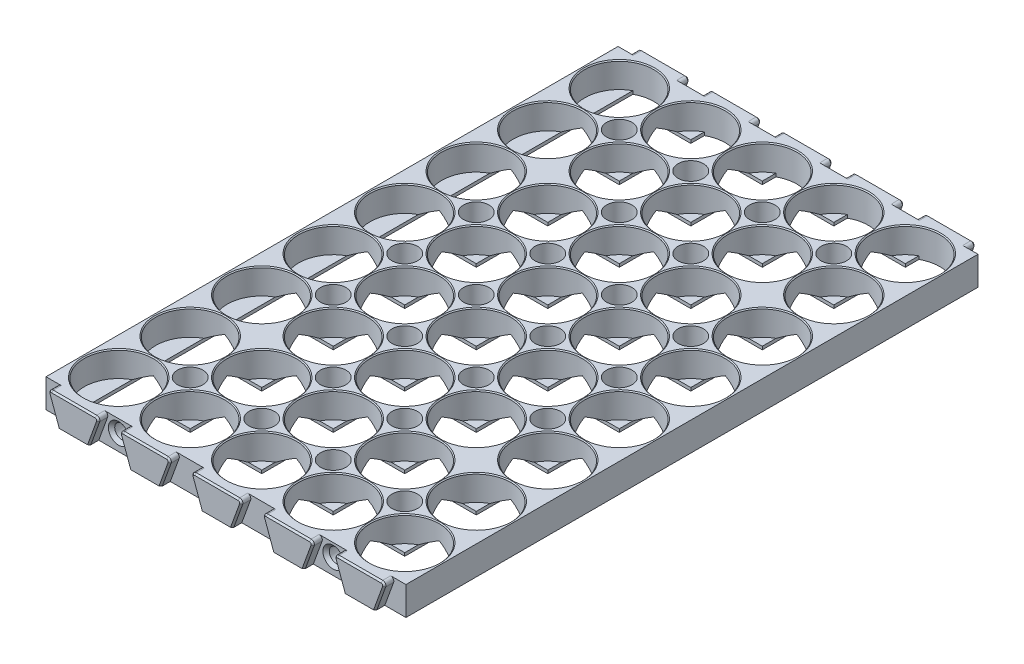
SolidWorks part; units mm, degrees
ref_plane "Front Plane" through (0, 0, 0) normal (0, 0, 1) x (1, 0, 0)
ref_plane "Top Plane" through (0, 0, 0) normal (0, 1, 0) x (1, 0, 0)
ref_plane "Right Plane" through (0, 0, 0) normal (1, 0, 0) x (0, 0, -1)
sketch "Sketch1" plane through (0, 0, 0) normal (0, 1, 0) x (1, 0, 0)
  line L0 (-11.25, 10.875) -> (11.25, 10.875) construction
  line L1 (-11.25, -11.25) -> (11.25, -11.25)
  line L2 (-11.25, -11.25) -> (-11.25, 11.25)
  line L3 (-11.25, 11.25) -> (11.25, 11.25)
  line L4 (11.25, -11.25) -> (11.25, 11.25)
  line L5 (-11.25, -11.25) -> (11.25, 11.25) construction
  line L6 (-11.25, 11.25) -> (11.25, -11.25) construction
  circle A0 centre (0, 0) radius 10.875
  point P0 (0, 0)
  dimension "D1" = 21.75
  dimension "D2" = 22.5
  dimension "D3" = 0.375
extrude "Boss-Extrude1" add sketch "Sketch1" along normal blind 8
sketch "Sketch2" plane through (0, 0, 0) normal (0, -1, 0) x (1, 0, 0)
  line L0 (5.25, 11.25) -> (-5.25, 11.25) construction
  line L1 (11.25, 11.25) -> (5.25, 11.25)
  line L2 (11.25, 11.25) -> (11.25, 5.25)
  line L3 (11.25, 5.25) -> (5.25, 5.25)
  line L4 (5.25, 11.25) -> (5.25, 5.25)
  line L5 (11.25, -11.25) -> (5.25, -11.25)
  line L6 (11.25, -11.25) -> (11.25, -5.25)
  line L7 (11.25, -5.25) -> (5.25, -5.25)
  line L8 (5.25, -11.25) -> (5.25, -5.25)
  line L9 (-11.25, -11.25) -> (-5.25, -11.25)
  line L10 (-11.25, -11.25) -> (-11.25, -5.25)
  line L11 (-11.25, -5.25) -> (-5.25, -5.25)
  line L12 (-5.25, -11.25) -> (-5.25, -5.25)
  line L13 (-11.25, 11.25) -> (-5.25, 11.25)
  line L14 (-11.25, 11.25) -> (-11.25, 5.25)
  line L15 (-11.25, 5.25) -> (-5.25, 5.25)
  line L16 (-5.25, 11.25) -> (-5.25, 5.25)
  line L17 (11.25, 5.25) -> (11.25, -5.25) construction
  line L18 (5.25, -11.25) -> (-5.25, -11.25) construction
  line L19 (-11.25, 5.25) -> (-11.25, -5.25) construction
  dimension "D1" = 10.5
extrude "Boss-Extrude2" add sketch "Sketch2" along normal blind 1
chamfer "Chamfer2" distance 0.3 angle 45 1 edges at (0, 8, 10.875)
pattern_linear "LPattern1" count 8 spacing 22.5 along (0, 0, 1) count 5 spacing 22.5 along (1, 0, 0) of "Boss-Extrude2", "Boss-Extrude1", "Chamfer2"
sketch "Sketch5" plane through (0, 0, -5.25) normal (0, 0, 1) x (1, 0, 0)
  line L25 (-5.25, -1) -> (-5.25, 0) construction
  line L26 (-5.25, -1) -> (-11.25, -1) construction
  line L27 (-11.25, -1) -> (-11.25, 0) construction
  line L29 (-5.25, 0) -> (-9.5238, 0) construction
  line L35 (-5.25, -1) -> (-5.25, 0)
  line L36 (-5.25, -1) -> (-11.25, -1)
  line L37 (-11.25, -1) -> (-11.25, 0)
  line L39 (-5.25, 0) -> (-11.25, 0)
  line L55 (101.25, -1) -> (95.25, -1)
  line L56 (101.25, -1) -> (101.25, 0)
  line L57 (101.25, 0) -> (95.25, 0)
  line L58 (95.25, -1) -> (95.25, 0)
  dimension "D1" = 6
extrude "Boss-Extrude3" add sketch "Sketch5" along normal up to surface (174 mm away)
sketch "Sketch6" plane through (0, 0, 0) normal (0, -1, 0) x (1, 0, 0)
  line L27 (39.75, -11.25) -> (50.25, -11.25) construction
  line L28 (50.25, -11.25) -> (50.25, -9.5238) construction
  line L29 (39.75, -9.5238) -> (39.75, -11.25) construction
  line L30 (17.25, -9.5238) -> (17.25, -11.25) construction
  line L31 (17.25, -11.25) -> (27.75, -11.25) construction
  line L32 (27.75, -11.25) -> (27.75, -9.5238) construction
  line L33 (-5.25, -9.5238) -> (-5.25, -11.25) construction
  line L34 (-5.25, -11.25) -> (5.25, -11.25) construction
  line L35 (5.25, -11.25) -> (5.25, -9.5238) construction
  line L51 (39.75, -11.25) -> (50.25, -11.25)
  line L52 (50.25, -11.25) -> (50.25, -9.5238)
  line L53 (39.75, -9.5238) -> (39.75, -11.25)
  line L54 (17.25, -9.5238) -> (17.25, -11.25)
  line L55 (17.25, -11.25) -> (27.75, -11.25)
  line L56 (27.75, -11.25) -> (27.75, -9.5238)
  line L57 (-5.25, -9.5238) -> (-5.25, -11.25)
  line L58 (-5.25, -11.25) -> (5.25, -11.25)
  line L59 (5.25, -11.25) -> (5.25, -9.5238)
  line L84 (5.25, 168.75) -> (-5.25, 168.75) construction
  line L85 (-5.25, 168.75) -> (-5.25, 167.0238) construction
  line L86 (5.25, 167.0238) -> (5.25, 168.75) construction
  line L87 (27.75, 167.0238) -> (27.75, 168.75) construction
  line L88 (27.75, 168.75) -> (17.25, 168.75) construction
  line L89 (17.25, 168.75) -> (17.25, 167.0238) construction
  line L93 (50.25, 167.0238) -> (50.25, 168.75) construction
  line L94 (50.25, 168.75) -> (39.75, 168.75) construction
  line L95 (39.75, 168.75) -> (39.75, 167.0238) construction
  line L96 (5.25, 168.75) -> (-5.25, 168.75)
  line L97 (-5.25, 168.75) -> (-5.25, 167.0238)
  line L98 (5.25, 167.0238) -> (5.25, 168.75)
  line L99 (27.75, 167.0238) -> (27.75, 168.75)
  line L100 (27.75, 168.75) -> (17.25, 168.75)
  line L101 (17.25, 168.75) -> (17.25, 167.0238)
  line L105 (50.25, 167.0238) -> (50.25, 168.75)
  line L106 (50.25, 168.75) -> (39.75, 168.75)
  line L107 (39.75, 168.75) -> (39.75, 167.0238)
  line L108 (84.75, -11.25) -> (95.25, -11.25) construction
  line L109 (95.25, -11.25) -> (95.25, -9.5238) construction
  line L110 (84.75, -9.5238) -> (84.75, -11.25) construction
  line L111 (95.25, 167.0238) -> (95.25, 168.75) construction
  line L112 (95.25, 168.75) -> (84.75, 168.75) construction
  line L113 (84.75, 168.75) -> (84.75, 167.0238) construction
  line L114 (72.75, 167.0238) -> (72.75, 168.75) construction
  line L115 (72.75, 168.75) -> (62.25, 168.75) construction
  line L116 (62.25, 168.75) -> (62.25, 167.0238) construction
  line L117 (84.75, -11.25) -> (95.25, -11.25)
  line L118 (95.25, -11.25) -> (95.25, -9.5238)
  line L119 (84.75, -9.5238) -> (84.75, -11.25)
  line L120 (95.25, 167.0238) -> (95.25, 168.75)
  line L121 (95.25, 168.75) -> (84.75, 168.75)
  line L122 (84.75, 168.75) -> (84.75, 167.0238)
  line L123 (72.75, 167.0238) -> (72.75, 168.75)
  line L124 (72.75, 168.75) -> (62.25, 168.75)
  line L125 (62.25, 168.75) -> (62.25, 167.0238)
  line L129 (62.25, -11.25) -> (72.75, -11.25)
  line L130 (72.75, -11.25) -> (72.75, -9.5238)
  line L131 (62.25, -9.5238) -> (62.25, -11.25)
  line L132 (62.25, -11.25) -> (72.75, -11.25)
  line L133 (72.75, -11.25) -> (72.75, -9.5238)
  line L134 (62.25, -9.5238) -> (62.25, -11.25)
  arc A9 (39.75, -9.5238) -> (50.25, -9.5238) centre (45, 0) ccw construction
  arc A10 (17.25, -9.5238) -> (27.75, -9.5238) centre (22.5, 0) ccw construction
  arc A11 (-5.25, -9.5238) -> (5.25, -9.5238) centre (0, 0) ccw construction
  arc A17 (39.75, -9.5238) -> (50.25, -9.5238) centre (45, 0) ccw
  arc A18 (17.25, -9.5238) -> (27.75, -9.5238) centre (22.5, 0) ccw
  arc A19 (-5.25, -9.5238) -> (5.25, -9.5238) centre (0, 0) ccw
  arc A28 (5.25, 167.0238) -> (-5.25, 167.0238) centre (0, 157.5) ccw construction
  arc A29 (27.75, 167.0238) -> (17.25, 167.0238) centre (22.5, 157.5) ccw construction
  arc A31 (50.25, 167.0238) -> (39.75, 167.0238) centre (45, 157.5) ccw construction
  arc A32 (5.25, 167.0238) -> (-5.25, 167.0238) centre (0, 157.5) ccw
  arc A33 (27.75, 167.0238) -> (17.25, 167.0238) centre (22.5, 157.5) ccw
  arc A35 (50.25, 167.0238) -> (39.75, 167.0238) centre (45, 157.5) ccw
  arc A36 (84.75, -9.5238) -> (95.25, -9.5238) centre (90, 0) ccw construction
  arc A37 (95.25, 167.0238) -> (84.75, 167.0238) centre (90, 157.5) ccw construction
  arc A38 (72.75, 167.0238) -> (62.25, 167.0238) centre (67.5, 157.5) ccw construction
  arc A39 (84.75, -9.5238) -> (95.25, -9.5238) centre (90, 0) ccw
  arc A40 (95.25, 167.0238) -> (84.75, 167.0238) centre (90, 157.5) ccw
  arc A41 (72.75, 167.0238) -> (62.25, 167.0238) centre (67.5, 157.5) ccw
  arc A43 (62.25, -9.5238) -> (72.75, -9.5238) centre (67.5, 0) ccw
  arc A44 (62.25, -9.5238) -> (72.75, -9.5238) centre (67.5, 0) ccw
  dimension "D1" = 0
extrude "Boss-Extrude4" add sketch "Sketch6" along normal up to surface (1 mm away) up to face at (-8.25, -1, 78.75)
sketch "Sketch7" plane through (0, 0, 0) normal (0, 0, 1) x (1, 0, 0)
  line L0 (-11.25, 8) -> (101.25, 8) construction
  line L1 (-5.25, 0) -> (5.25, 0)
  line L2 (-5.25, 0) -> (0, 5.25) construction
  line L3 (0, 5.25) -> (5.25, 0) construction
  line L4 (0, 0) -> (0, 8) construction
  line L5 (84.75, 0) -> (90, 3.0311)
  line L6 (-5.25, 0) -> (0, 3.0311)
  line L7 (0, 3.0311) -> (5.25, 0)
  line L8 (90, 3.0311) -> (95.25, 0)
  line L9 (-5.25, -1) -> (-5.25, 0) construction
  line L10 (5.25, -1) -> (5.25, 0) construction
  line L11 (-5.25, -1) -> (-5.25, 0) construction
  line L12 (5.25, -1) -> (5.25, 0) construction
  line L13 (17.25, 0) -> (22.5, 3.0311)
  line L14 (22.5, 3.0311) -> (27.75, 0)
  line L15 (17.25, 0) -> (27.75, 0)
  line L16 (39.75, 0) -> (45, 3.0311)
  line L17 (45, 3.0311) -> (50.25, 0)
  line L18 (39.75, 0) -> (50.25, 0)
  line L19 (62.25, 0) -> (67.5, 3.0311)
  line L20 (67.5, 3.0311) -> (72.75, 0)
  line L21 (62.25, 0) -> (72.75, 0)
  line L22 (-5.25, 0) -> (17.25, 0) construction
  line L23 (84.75, 0) -> (95.25, 0)
  dimension "D1" = 45
  dimension "D2" = 30
  dimension "D3" = 4.9689
  dimension "D5" = 22.5
  dimension "D4" = 5
extrude "Cut-Extrude1" cut sketch "Sketch7" along normal up to surface (162.75 mm away) up to face at (56.25, -0.3333, 162.75)
sketch "Sketch16" plane through (0, 0, 0) normal (1, 0, 0) x (0, 0, -1)
  line L2 (-5.25, -1) -> (-5.25, 0) construction
  line L3 (5.25, -1) -> (5.25, 0) construction
  line L4 (-5.25, 0) -> (0, 3.0311)
  line L5 (0, 3.0311) -> (5.25, 0)
  line L6 (-5.25, 0) -> (5.25, 0)
  line L7 (-5.25, -1) -> (-5.25, 0) construction
  line L8 (5.25, -1) -> (5.25, 0) construction
  line L9 (-22.5, 3.0311) -> (-17.25, 0)
  line L10 (-27.75, 0) -> (-17.25, 0)
  line L11 (-27.75, 0) -> (-22.5, 3.0311)
  line L12 (-45, 3.0311) -> (-39.75, 0)
  line L13 (-50.25, 0) -> (-39.75, 0)
  line L14 (-50.25, 0) -> (-45, 3.0311)
  line L15 (-67.5, 3.0311) -> (-62.25, 0)
  line L16 (-72.75, 0) -> (-62.25, 0)
  line L17 (-72.75, 0) -> (-67.5, 3.0311)
  line L18 (-90, 3.0311) -> (-84.75, 0)
  line L19 (-95.25, 0) -> (-84.75, 0)
  line L20 (-95.25, 0) -> (-90, 3.0311)
  line L21 (-112.5, 3.0311) -> (-107.25, 0)
  line L22 (-117.75, 0) -> (-107.25, 0)
  line L23 (-117.75, 0) -> (-112.5, 3.0311)
  line L24 (-135, 3.0311) -> (-129.75, 0)
  line L25 (-140.25, 0) -> (-129.75, 0)
  line L26 (-140.25, 0) -> (-135, 3.0311)
  line L27 (-157.5, 3.0311) -> (-152.25, 0)
  line L28 (-162.75, 0) -> (-152.25, 0)
  line L29 (-162.75, 0) -> (-157.5, 3.0311)
  line L42 (0, 3.0311) -> (-22.5, 3.0311) construction
  dimension "D1" = 30
  dimension "D3" = 22.5
  dimension "D2" = 8
extrude "Cut-Extrude7" cut sketch "Sketch16" along normal up to surface (84.75 mm away) up to face at (84.75, -0.3333, 11.25)
sketch "Sketch8" plane through (0, 0, -11.25) normal (0, 0, -1) x (-1, 0, 0)
  line L0 (0, -1) -> (0, 8) construction
  line L1 (-27.4743, -1) -> (-30.75, 8)
  line L2 (-101.25, 8) -> (11.25, 8) construction
  line L3 (4.9743, -1) -> (-4.9743, -1)
  line L4 (-4.9743, -1) -> (-8.25, 8)
  line L5 (-8.25, 8) -> (8.25, 8)
  line L6 (4.9743, -1) -> (8.25, 8)
  line L7 (11.25, 8) -> (11.25, -1) construction
  line L8 (11.25, -1) -> (-101.25, -1) construction
  line L9 (-30.75, 8) -> (-14.25, 8)
  line L10 (-101.25, 8) -> (11.25, 8) construction
  line L11 (-17.5257, -1) -> (-14.25, 8)
  line L12 (-17.5257, -1) -> (-27.4743, -1)
  line L13 (-49.9743, -1) -> (-53.25, 8)
  line L14 (-53.25, 8) -> (-36.75, 8)
  line L15 (-40.0257, -1) -> (-36.75, 8)
  line L16 (-40.0257, -1) -> (-49.9743, -1)
  line L17 (-72.4743, -1) -> (-75.75, 8)
  line L18 (-75.75, 8) -> (-59.25, 8)
  line L19 (-62.5257, -1) -> (-59.25, 8)
  line L20 (-62.5257, -1) -> (-72.4743, -1)
  line L21 (-4.9743, -1) -> (-27.4743, -1) construction
  line L22 (-101.25, 8) -> (11.25, 8) construction
  line L23 (-94.9743, -1) -> (-98.25, 8)
  line L24 (-98.25, 8) -> (-81.75, 8)
  line L25 (-85.0257, -1) -> (-81.75, 8)
  line L26 (-85.0257, -1) -> (-94.9743, -1)
  dimension "D1" = 70
  dimension "D2" = 3
  dimension "D4" = 22.5
  dimension "D5" = 9
sketch "Sketch9" plane through (0, 0, 168.75) normal (0, 0, 1) x (1, 0, 0)
  line L0 (85.0257, -1) -> (94.9743, -1) construction
  line L3 (85.0257, -1) -> (81.75, 8) construction
  line L20 (94.9743, -1) -> (98.25, 8) construction
  line L21 (98.25, 8) -> (81.75, 8) construction
  line L22 (85.0257, -1) -> (94.9743, -1)
  line L23 (85.0257, -1) -> (81.75, 8)
  line L24 (-4.9743, -1) -> (4.9743, -1)
  line L25 (4.9743, -1) -> (8.25, 8)
  line L26 (8.25, 8) -> (-8.25, 8)
  line L27 (-8.25, 8) -> (-4.9743, -1)
  line L28 (-4.9743, -1) -> (4.9743, -1)
  line L29 (4.9743, -1) -> (8.25, 8)
  line L30 (8.25, 8) -> (-8.25, 8)
  line L31 (-8.25, 8) -> (-4.9743, -1)
  line L32 (72.4743, -1) -> (75.75, 8)
  line L33 (75.75, 8) -> (59.25, 8)
  line L34 (59.25, 8) -> (62.5257, -1)
  line L35 (62.5257, -1) -> (72.4743, -1)
  line L36 (72.4743, -1) -> (75.75, 8)
  line L37 (75.75, 8) -> (59.25, 8)
  line L38 (59.25, 8) -> (62.5257, -1)
  line L39 (62.5257, -1) -> (72.4743, -1)
  line L40 (49.9743, -1) -> (53.25, 8)
  line L41 (53.25, 8) -> (36.75, 8)
  line L42 (36.75, 8) -> (40.0257, -1)
  line L43 (40.0257, -1) -> (49.9743, -1)
  line L44 (49.9743, -1) -> (53.25, 8)
  line L45 (53.25, 8) -> (36.75, 8)
  line L46 (36.75, 8) -> (40.0257, -1)
  line L47 (40.0257, -1) -> (49.9743, -1)
  line L48 (14.25, 8) -> (17.5257, -1)
  line L49 (17.5257, -1) -> (27.4743, -1)
  line L50 (27.4743, -1) -> (30.75, 8)
  line L51 (30.75, 8) -> (14.25, 8)
  line L52 (14.25, 8) -> (17.5257, -1)
  line L53 (17.5257, -1) -> (27.4743, -1)
  line L54 (27.4743, -1) -> (30.75, 8)
  line L55 (30.75, 8) -> (14.25, 8)
  line L56 (94.9743, -1) -> (98.25, 8)
  line L57 (98.25, 8) -> (81.75, 8)
  dimension "D1" = 0
  dimension "D2" = 0
  dimension "D3" = 0
  dimension "D4" = 0
extrude "Boss-Extrude5" add sketch "Sketch8" along normal blind 3
extrude "Boss-Extrude6" add sketch "Sketch9" along normal blind 3
fillet "Fillet1" radius 1 20 edges at (98.25, 8, -12.75) (81.75, 8, -12.75) (75.75, 8, -12.75) (59.25, 8, -12.75) (53.25, 8, -12.75) (36.75, 8, -12.75) (30.75, 8, -12.75) (14.25, 8, -12.75) (8.25, 8, -12.75) (-8.25, 8, -12.75) (-8.25, 8, 170.25) (8.25, 8, 170.25) (14.25, 8, 170.25) (30.75, 8, 170.25) (36.75, 8, 170.25) (53.25, 8, 170.25) (59.25, 8, 170.25) (75.75, 8, 170.25) (81.75, 8, 170.25) (98.25, 8, 170.25)
chamfer "Chamfer3" distance 0.5 angle 45 50 edges at (6.3679, 2.829, -14.25) (0, 8, -14.25) (-6.3679, 2.829, -14.25) (73.8679, 2.829, -14.25) (67.5, 8, -14.25) (61.1321, 2.829, -14.25) (51.3679, 2.829, -14.25) (45, 8, -14.25) (38.6321, 2.829, -14.25) (28.8679, 2.829, -14.25) (22.5, 8, -14.25) (16.1321, 2.829, -14.25) (73.8679, 2.829, 171.75) (61.1321, 2.829, 171.75) (67.5, 8, 171.75) (51.3679, 2.829, 171.75) (38.6321, 2.829, 171.75) (45, 8, 171.75) (28.8679, 2.829, 171.75) (16.1321, 2.829, 171.75) (22.5, 8, 171.75) (6.3679, 2.829, 171.75) (-6.3679, 2.829, 171.75) (0, 8, 171.75) (83.6321, 2.829, -14.25) (90, 8, -14.25) (96.3679, 2.829, -14.25) (96.3679, 2.829, 171.75) (90, 8, 171.75) (83.6321, 2.829, 171.75) (82.359, 7.5736, -14.25) (97.641, 7.5736, -14.25) (97.641, 7.5736, 171.75) (82.359, 7.5736, 171.75) (75.141, 7.5736, 171.75) (59.859, 7.5736, 171.75) (52.641, 7.5736, 171.75) (37.359, 7.5736, 171.75) (30.141, 7.5736, 171.75) (14.859, 7.5736, 171.75) (7.641, 7.5736, 171.75) (-7.641, 7.5736, 171.75) (75.141, 7.5736, -14.25) (59.859, 7.5736, -14.25) (52.641, 7.5736, -14.25) (37.359, 7.5736, -14.25) (30.141, 7.5736, -14.25) (14.859, 7.5736, -14.25) (7.641, 7.5736, -14.25) (-7.641, 7.5736, -14.25)
sketch "Sketch10" plane through (0, 0, -11.25) normal (0, 0, -1) x (-1, 0, 0)
  line L0 (-11.25, -1) -> (-11.25, 8) construction
  line L1 (-49.4422, -1) -> (-40.5578, -1) construction
  line L2 (-4.9743, -1) -> (-17.5257, -1) construction
  line L3 (-51.8219, 8) -> (-38.1781, 8) construction
  line L4 (-14.25, 8) -> (-8.25, 8) construction
  line L5 (-45, 8) -> (-45, -1) construction
  circle A0 centre (-11.25, 4) radius 2.25
  circle A1 centre (-78.75, 4) radius 2.25
  dimension "D2" = 4.5
  dimension "D1" = 4
sketch "Sketch11" plane through (0, 0, 168.75) normal (0, 0, 1) x (1, 0, 0)
  circle A0 centre (11.25, 4) radius 2.25 construction
  circle A1 centre (11.25, 4) radius 2.25
  circle A2 centre (78.75, 4) radius 2.25 construction
  circle A3 centre (78.75, 4) radius 2.25
extrude "Cut-Extrude2" cut sketch "Sketch10" against normal blind 5
extrude "Cut-Extrude3" cut sketch "Sketch11" against normal blind 5
chamfer "Chamfer5" distance 1 angle 45 4 edges at (81, 4, -11.25) (9, 4, -11.25) (13.5, 4, 168.75) (81, 4, 168.75)
sketch "Sketch17" plane through (0, -1, 0) normal (0, -1, 0) x (1, 0, 0)
  line L0 (5.25, 5.25) -> (17.25, 17.25) construction
  line L1 (11.25, 11.25) -> (33.75, 11.25) construction
  circle A0 centre (11.25, 11.25) radius 4
  circle A1 centre (33.75, 11.25) radius 4
  circle A2 centre (56.25, 11.25) radius 4
  circle A33 centre (33.75, 146.25) radius 4 [skipped]
  circle A34 centre (56.25, 146.25) radius 4 [skipped]
  circle A35 centre (33.75, 168.75) radius 4 [skipped]
  circle A36 centre (33.75, 191.25) radius 4 [skipped]
  circle A37 centre (56.25, 191.25) radius 4 [skipped]
  circle A38 centre (33.75, 213.75) radius 4 [skipped]
  circle A39 centre (56.25, 213.75) radius 4 [skipped]
  circle A40 centre (33.75, 236.25) radius 4 [skipped]
  circle A41 centre (56.25, 236.25) radius 4 [skipped]
  circle A42 centre (11.25, 146.25) radius 4 [skipped]
  circle A43 centre (11.25, 191.25) radius 4 [skipped]
  circle A44 centre (11.25, 213.75) radius 4 [skipped]
  circle A45 centre (11.25, 236.25) radius 4 [skipped]
  circle A46 centre (56.25, 168.75) radius 4 construction
  circle A47 centre (11.25, 168.75) radius 4 construction
  circle A48 centre (33.75, 123.75) radius 4 [skipped]
  circle A49 centre (56.25, 123.75) radius 4 [skipped]
  circle A50 centre (11.25, 123.75) radius 4 [skipped]
  circle A57 centre (33.75, 33.75) radius 4 [skipped]
  circle A58 centre (33.75, 56.25) radius 4 [skipped]
  circle A59 centre (56.25, 56.25) radius 4 [skipped]
  circle A60 centre (33.75, 78.75) radius 4 [skipped]
  circle A61 centre (56.25, 78.75) radius 4 [skipped]
  circle A62 centre (33.75, 101.25) radius 4 [skipped]
  circle A63 centre (56.25, 101.25) radius 4 [skipped]
  circle A64 centre (11.25, 56.25) radius 4 [skipped]
  circle A65 centre (11.25, 78.75) radius 4 [skipped]
  circle A66 centre (11.25, 101.25) radius 4 [skipped]
  circle A67 centre (56.25, 33.75) radius 4 construction
  circle A68 centre (11.25, 33.75) radius 4 construction
  circle A69 centre (11.25, 33.75) radius 4 construction
  circle A70 centre (33.75, 33.75) radius 4
  circle A71 centre (56.25, 33.75) radius 4
  circle A72 centre (11.25, 56.25) radius 4
  circle A73 centre (33.75, 56.25) radius 4
  circle A74 centre (56.25, 56.25) radius 4
  circle A75 centre (11.25, 78.75) radius 4
  circle A76 centre (33.75, 78.75) radius 4
  circle A77 centre (56.25, 78.75) radius 4
  circle A78 centre (11.25, 101.25) radius 4
  circle A79 centre (33.75, 101.25) radius 4
  circle A80 centre (56.25, 101.25) radius 4
  circle A81 centre (11.25, 123.75) radius 4 construction
  circle A82 centre (33.75, 123.75) radius 4
  circle A83 centre (56.25, 123.75) radius 4
  circle A84 centre (11.25, 146.25) radius 4
  circle A85 centre (33.75, 146.25) radius 4
  circle A86 centre (56.25, 146.25) radius 4
  circle A87 centre (11.25, 258.75) radius 4 [skipped]
  circle A88 centre (33.75, 258.75) radius 4 [skipped]
  circle A89 centre (56.25, 258.75) radius 4 [skipped]
  circle A90 centre (11.25, 281.25) radius 4 [skipped]
  circle A91 centre (33.75, 281.25) radius 4 [skipped]
  circle A92 centre (56.25, 281.25) radius 4 [skipped]
  circle A93 centre (78.75, 11.25) radius 4
  circle A94 centre (78.75, 33.75) radius 4 construction
  circle A95 centre (78.75, 56.25) radius 4
  circle A96 centre (78.75, 78.75) radius 4
  circle A97 centre (78.75, 101.25) radius 4
  circle A98 centre (78.75, 123.75) radius 4 construction
  circle A99 centre (78.75, 146.25) radius 4
  circle A106 centre (78.75, 168.75) radius 4 [skipped]
  circle A107 centre (78.75, 191.25) radius 4 [skipped]
  circle A108 centre (78.75, 213.75) radius 4 [skipped]
  circle A109 centre (78.75, 236.25) radius 4 [skipped]
  circle A110 centre (78.75, 258.75) radius 4 [skipped]
  circle A111 centre (78.75, 281.25) radius 4 [skipped]
  dimension "D4" = 22.5
  dimension "D1" = 8
  dimension "D2" = 4
  dimension "D3" = 13
  dimension "D5" = 7
extrude "Cut-Extrude8" cut sketch "Sketch17" against normal through all
sketch "Sketch18" plane through (0, -1, 0) normal (0, -1, 0) x (1, 0, 0)
  line L2 (5.25, 117.75) -> (17.25, 129.75) construction
  line L3 (5.25, 27.75) -> (17.25, 39.75) construction
  line L4 (72.75, 27.75) -> (84.75, 39.75) construction
  line L5 (101.25, -11.25) -> (101.25, 168.75) construction
  line L6 (84.75, 129.75) -> (72.75, 129.75) construction
  line L38 (101.25, 78.75) -> (-11.25, 78.75) construction
  line L40 (-11.25, 168.75) -> (-11.25, -11.25) construction
  line L42 (72.75, 117.75) -> (84.75, 129.75) construction
  circle A0 centre (11.25, 33.75) radius 2.1
  circle A4 centre (78.75, 33.75) radius 2.1
  circle A7 centre (78.75, 123.75) radius 2.1
  circle A8 centre (11.25, 123.75) radius 2.1
  dimension "D1" = 4.2
extrude "Cut-Extrude9" cut sketch "Sketch18" against normal blind 4
sketch "Sketch19" plane through (0, -1, 0) normal (0, -1, 0) x (1, 0, 0)
  line L0 (101.25, 78.75) -> (-11.25, 78.75) construction
  line L2 (-11.25, 168.75) -> (-11.25, -11.25) construction
  line L3 (101.25, -11.25) -> (101.25, 168.75) construction
  circle A2 centre (78.75, 123.75) radius 1.7
  circle A3 centre (11.25, 33.75) radius 1.7
  circle A4 centre (11.25, 123.75) radius 1.7
  circle A5 centre (78.75, 33.75) radius 1.7
  dimension "D1" = 3.4
extrude "Cut-Extrude10" cut sketch "Sketch19" against normal offset from surface (7 mm away) 2 up to face at (78.75, 8, 97.25)
chamfer "Chamfer6" distance 1 angle 45 4 edges at (11.25, -1, 121.65) (11.25, -1, 31.65) (78.75, -1, 31.65) (78.75, -1, 121.65)
sketch "Sketch22" plane through (0, 8, 0) normal (0, 1, 0) x (1, 0, 0)
  line L0 (-11.25, -168.75) -> (-6.8219, -168.75) construction
  line L1 (-11.25, 11.25) -> (-11.625, 11.25)
  line L2 (-11.25, 11.25) -> (-11.25, -168.75)
  line L3 (-11.25, -168.75) -> (-11.625, -168.75)
  line L4 (-11.625, 11.25) -> (-11.625, -168.75)
  line L5 (45, 14.25) -> (45, -171.75) construction
  line L12 (51.8219, -171.75) -> (38.1781, -171.75) construction
  line L13 (38.1781, 14.25) -> (51.8219, 14.25) construction
  line L14 (101.625, 11.25) -> (101.625, -168.75)
  line L15 (101.25, -168.75) -> (101.625, -168.75)
  line L16 (101.25, 11.25) -> (101.25, -168.75)
  line L17 (101.25, 11.25) -> (101.625, 11.25)
  arc A1 (-5.25, 9.5238) -> (-5.25, -9.5238) centre (0, 0) ccw construction
  point P10 (-10.875, 0)
  dimension "D1" = 0.75
  dimension "D2" = 0.375
extrude "Boss-Extrude7" add sketch "Sketch22" against normal up to surface (9 mm away) up to face at (45, -1, 78.75)
sketch "Sketch14" plane through (0, -1, 0) normal (0, -1, 0) x (1, 0, 0)
  line L0 (-10.25, 76.2941) -> (-10.25, 81.2059)
  line L2 (-10.25, 78.75) -> (-11.625, 78.75) construction
  line L4 (45, -14.25) -> (45, 171.75) construction
  line L19 (49.4422, -14.25) -> (40.5578, -14.25) construction
  line L30 (40.5578, 171.75) -> (49.4422, 171.75) construction
  line L39 (-6.25, 77.75) -> (-6.25, 79.75)
  line L40 (-10.25, 8.7941) -> (-10.25, 13.7059)
  line L51 (-6.25, 10.25) -> (-6.25, 12.25)
  line L52 (-5.25, 146.25) -> (-6.25, 146.25) construction
  line L54 (-10.25, 13.7059) -> (-6.25, 12.25)
  line L55 (-6.25, 146.25) -> (-10.25, 146.25) construction
  line L56 (-10.25, 146.25) -> (-11.625, 146.25) construction
  line L57 (-10.25, 81.2059) -> (-6.25, 79.75)
  line L58 (-5.25, -9.5238) -> (-5.25, 167.0238) construction
  line L59 (-10.25, 148.7059) -> (-6.25, 147.25)
  line L60 (-10.25, 143.7941) -> (-6.25, 145.25)
  line L61 (-6.25, 147.25) -> (-6.25, 145.25)
  line L62 (-10.25, 148.7059) -> (-10.25, 143.7941)
  line L64 (95.25, 78.75) -> (96.25, 78.75) construction
  line L65 (96.25, 78.75) -> (100.25, 78.75) construction
  line L66 (95.25, 11.25) -> (96.25, 11.25) construction
  line L67 (96.25, 11.25) -> (100.25, 11.25) construction
  line L68 (-5.25, 9.5238) -> (-5.25, 12.9762) construction
  line L69 (-10.25, 11.25) -> (-11.625, 11.25) construction
  line L70 (-6.25, 11.25) -> (-10.25, 11.25) construction
  line L71 (-5.25, 11.25) -> (-6.25, 11.25) construction
  line L75 (-10.25, 8.7941) -> (-6.25, 10.25)
  line L76 (100.25, 11.25) -> (101.625, 11.25) construction
  line L77 (100.25, 146.25) -> (101.625, 146.25) construction
  line L78 (96.25, 146.25) -> (100.25, 146.25) construction
  line L79 (95.25, 146.25) -> (96.25, 146.25) construction
  line L84 (100.25, 78.75) -> (101.625, 78.75) construction
  line L85 (100.25, 76.2941) -> (96.25, 77.75)
  line L86 (100.25, 8.7941) -> (96.25, 10.25)
  line L87 (100.25, 148.7059) -> (100.25, 143.7941)
  line L93 (96.25, 147.25) -> (96.25, 145.25)
  line L94 (-6.25, 78.75) -> (-10.25, 78.75) construction
  line L95 (-5.25, 78.75) -> (-6.25, 78.75) construction
  line L98 (-10.25, 76.2941) -> (-6.25, 77.75)
  line L99 (100.25, 143.7941) -> (96.25, 145.25)
  line L100 (100.25, 148.7059) -> (96.25, 147.25)
  line L101 (100.25, 81.2059) -> (96.25, 79.75)
  line L102 (100.25, 13.7059) -> (96.25, 12.25)
  line L103 (96.25, 10.25) -> (96.25, 12.25)
  line L104 (100.25, 8.7941) -> (100.25, 13.7059)
  line L105 (96.25, 77.75) -> (96.25, 79.75)
  line L106 (100.25, 76.2941) -> (100.25, 81.2059)
  line L107 (-11.625, -11.25) -> (-11.625, 168.75) construction
  point P59 (96.25, 78.75)
  dimension "D1" = 70
  dimension "D2" = 4
  dimension "D3" = 1
  dimension "D4" = 4
  dimension "D5" = 1.375
  dimension "D7" = 70
  dimension "D9" = 1
extrude "Cut-Extrude11" cut sketch "Sketch14" against normal blind 2
chamfer "Chamfer7" distance 0.5 angle 45 24 edges at (96.25, -1, 146.25) (98.25, -1, 144.5221) (100.25, -1, 146.25) (98.25, -1, 147.9779) (-10.25, -1, 146.25) (-8.25, -1, 144.5221) (-6.25, -1, 146.25) (-8.25, -1, 147.9779) (-8.25, -1, 77.0221) (-10.25, -1, 78.75) (-8.25, -1, 80.4779) (-6.25, -1, 78.75) (96.25, -1, 78.75) (98.25, -1, 77.0221) (100.25, -1, 78.75) (98.25, -1, 80.4779) (98.25, -1, 9.5221) (96.25, -1, 11.25) (98.25, -1, 12.9779) (100.25, -1, 11.25) (-10.25, -1, 11.25) (-8.25, -1, 12.9779) (-6.25, -1, 11.25) (-8.25, -1, 9.5221)
equation "\"cell_side\"= 22.50"
equation "\"D2@Sketch1\"=\"cell_side\""
equation "\"D5@Sketch7\"=\"cell_side\""
equation "\"D3@Sketch16\"=\"cell_side\""
equation "\"D4@Sketch8\"=\"cell_side\""
equation "\"D3@LPattern1\"=\"cell_side\""
equation "\"D4@LPattern1\"=\"cell_side\""
equation "\"D4@Sketch17\"=\"cell_side\""
